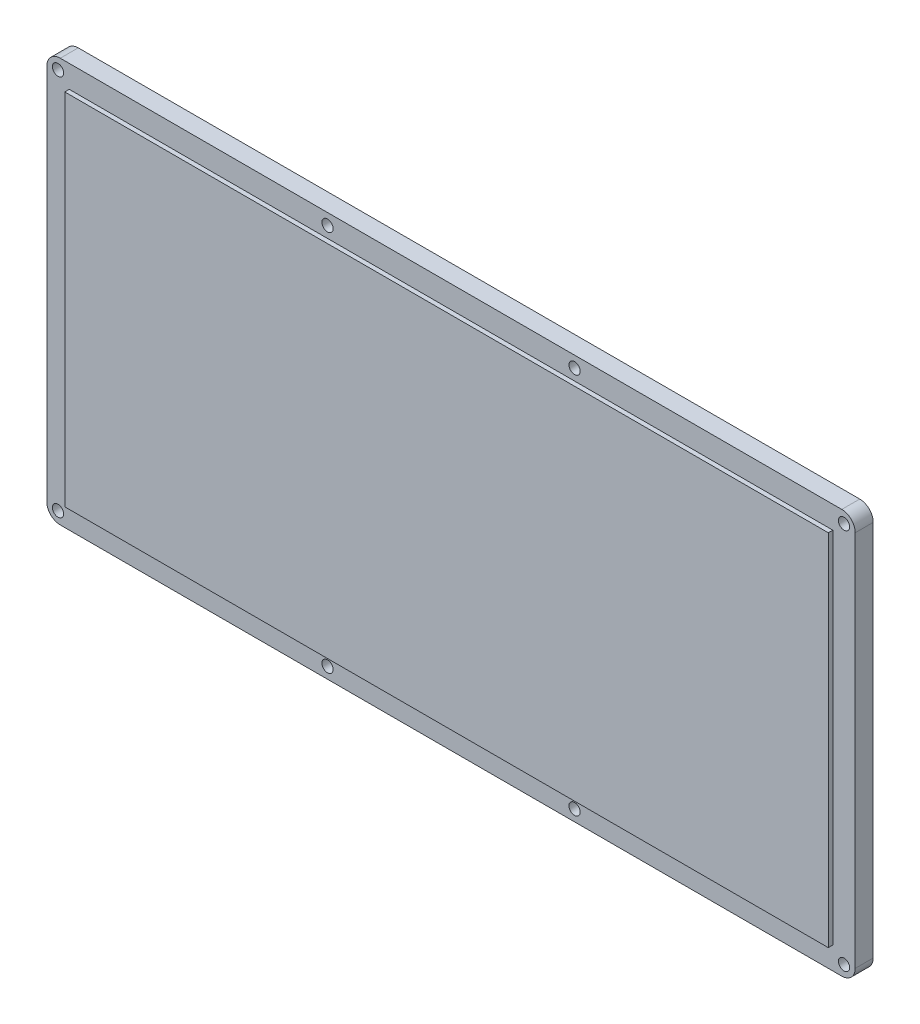
SolidWorks part; units mm, degrees
ref_plane "Front Plane" through (0, 0, 0) normal (0, 0, 1) x (1, 0, 0)
ref_plane "Top Plane" through (0, 0, 0) normal (0, 1, 0) x (1, 0, 0)
ref_plane "Right Plane" through (0, 0, 0) normal (1, 0, 0) x (0, 0, -1)
sketch "Sketch1" plane through (0, 0, 0) normal (0, 0, 1) x (1, 0, 0)
  line L1 (-90, 45) -> (90, 45)
  line L2 (-90, 45) -> (-90, -45)
  line L3 (-90, -45) -> (90, -45)
  line L4 (90, 45) -> (90, -45)
  point P4 (0, 45)
  point P6 (-90, 0)
  dimension "D1" = 180
  dimension "D2" = 90
extrude "Boss-Extrude1" add sketch "Sketch1" along normal blind 4
fillet "Fillet1" radius 3 4 edges at (90, 45, 2) (90, -45, 2) (-90, -45, 2) (-90, 45, 2)
sketch "Sketch2" plane through (0, 0, 4) normal (0, 0, 1) x (1, 0, 0)
  line L8 (85, -40) -> (85, 40)
  line L9 (85, 40) -> (-85, 40)
  line L10 (-85, 40) -> (-85, -40)
  line L11 (-85, -40) -> (85, -40)
  line L12 (85, -40) -> (85, 40)
  line L13 (85, 40) -> (-85, 40)
  line L14 (-85, 40) -> (-85, -40)
  line L15 (-85, -40) -> (85, -40)
  dimension "D1" = 5
extrude "Boss-Extrude2" add sketch "Sketch2" along normal blind 1
sketch "Sketch3" plane through (0, 0, 0) normal (0, 0, -1) x (-1, 0, 0)
  line L1 (-87.5, 42.5) -> (87.5, 42.5) construction
  line L2 (-87.5, 42.5) -> (-87.5, -42.5) construction
  line L3 (-87.5, -42.5) -> (87.5, -42.5) construction
  line L4 (87.5, 42.5) -> (87.5, -42.5) construction
  line L5 (-90, -42) -> (-90, 42) construction
  line L6 (-87, 45) -> (87, 45) construction
  circle A0 centre (-87.5, 42.5) radius 1.25
  circle A1 centre (87.5, 42.5) radius 1.25
  circle A2 centre (87.5, -42.5) radius 1.25
  circle A3 centre (-87.5, -42.5) radius 1.25
  circle A4 centre (-27.5, -42.5) radius 1.25
  circle A5 centre (27.5, 42.5) radius 1.25
  circle A6 centre (27.5, -42.5) radius 1.25
  circle A7 centre (-27.5, 42.5) radius 1.25
  point P4 (0, 42.5)
  point P6 (-87.5, 0)
  dimension "D1" = 2.5
  dimension "D4" = 2.5
  dimension "D5" = 2.5
  dimension "D6" = 60
  dimension "D7" = 2.5
  dimension "D8" = 60
  dimension "D9" = 60
  dimension "D10" = 2.5
  dimension "D2" = 2.5
  dimension "D3" = 2.5
  dimension "D11" = 60
extrude "Cut-Extrude2" cut sketch "Sketch3" against normal blind 10
sketch "Sketch4" plane through (0, 0, 0) normal (0, 0, -1) x (-1, 0, 0)
  line L0 (33.3333, 100) -> (166.6667, 100) construction
  line L1 (47.5892, 25.146) -> (-47.5892, 25.146)
  line L2 (-71.4139, 1.3212) -> (-71.4139, -1.3212)
  line L3 (-47.5892, -25.146) -> (47.5892, -25.146)
  line L4 (71.4139, -1.3212) -> (71.4139, 1.3212)
  line L5 (-27.9881, -11.6905) -> (-26.7934, -10.7431)
  line L6 (-13.3429, 2.4562) -> (-15.6911, 2.4562)
  line L7 (-5.6806, 7.8767) -> (-6.8547, 6.9073)
  line L8 (-15.6911, 4.0426) -> (-13.3429, 4.0426)
  line L9 (-13.3429, -0.717) -> (-15.6911, -0.717)
  line L10 (-3.3529, 9.8599) -> (-4.5065, 8.8684)
  line L11 (-15.6911, 0.8696) -> (-13.4254, 0.8696)
  line L12 (-25.6812, -9.7075) -> (-24.5277, -8.7158)
  line L13 (-15.6911, -2.3036) -> (-13.4254, -2.3036)
  line L14 (-23.3536, -7.7241) -> (-22.1795, -6.7547)
  line L15 (-13.3429, -3.8901) -> (-15.6911, -3.8901)
  line L16 (-1.046, 11.8431) -> (-2.2406, 10.8955)
  line L17 (24.3308, -5.2744) -> (25.4636, -6.2219)
  line L18 (25.4842, 6.7341) -> (24.3101, 5.828)
  line L19 (26.6583, -7.1282) -> (27.7706, -8.0963)
  line L20 (27.8118, 8.588) -> (26.6583, 7.6612)
  line L21 (28.9242, -9.0232) -> (30.0982, -9.9297)
  line L22 (30.1188, 10.4419) -> (28.9242, 9.5561)
  line L23 (55.4131, -5.2744) -> (56.5459, -6.2219)
  line L24 (56.5664, 6.7341) -> (55.3923, 5.828)
  line L25 (57.7405, -7.1282) -> (58.8529, -8.0963)
  line L26 (58.8941, 8.588) -> (57.7405, 7.6612)
  line L27 (60.0064, -9.0232) -> (61.1805, -9.9297)
  line L28 (61.201, 10.4419) -> (60.0064, 9.5561)
  spline S0 degree 3 poles (-35.6815, 4.87) (-36.3065, 6.3326) (-37.151, 7.5957) (-38.2151, 8.6602) knots 15 15 15 15 16 16 16 16
  spline S1 degree 3 poles (-35.6815, -4.3373) (-35.0569, -2.8747) (-34.7443, -1.3401) (-34.7443, 0.2666) (-34.7443, 1.8732) (-35.0569, 3.4076) (-35.6815, 4.87) knots 13 13 13 13 14 14 14 15 15 15 15
  spline S2 degree 3 poles (-38.2151, -8.1271) (-37.151, -7.0632) (-36.3065, -5.7996) (-35.6815, -4.3373) knots 12 12 12 12 13 13 13 13
  spline S3 degree 3 poles (-42.0051, -10.6608) (-40.5426, -10.0362) (-39.2794, -9.1916) (-38.2151, -8.1271) knots 11 11 11 11 12 12 12 12
  spline S4 degree 3 poles (-51.2124, -10.6608) (-49.7499, -11.2858) (-48.2153, -11.5979) (-46.6087, -11.5979) (-45.0021, -11.5979) (-43.4676, -11.2858) (-42.0051, -10.6608) knots 9 9 9 9 10 10 10 11 11 11 11
  spline S5 degree 3 poles (-55.0024, -8.1271) (-53.9384, -9.1916) (-52.6748, -10.0362) (-51.2124, -10.6608) knots 8 8 8 8 9 9 9 9
  spline S6 degree 3 poles (-57.536, -4.3373) (-56.9113, -5.7996) (-56.0668, -7.0632) (-55.0024, -8.1271) knots 7 7 7 7 8 8 8 8
  spline S7 degree 3 poles (-57.536, 4.87) (-58.161, 3.4076) (-58.4732, 1.8732) (-58.4732, 0.2666) (-58.4732, -1.3401) (-58.161, -2.8747) (-57.536, -4.3373) knots 5 5 5 5 6 6 6 7 7 7 7
  spline S8 degree 3 poles (-55.0024, 8.6602) (-56.0668, 7.5957) (-56.9113, 6.3326) (-57.536, 4.87) knots 4 4 4 4 5 5 5 5
  spline S9 degree 3 poles (-51.2124, 11.1937) (-52.6748, 10.5686) (-53.9384, 9.7242) (-55.0024, 8.6602) knots 3 3 3 3 4 4 4 4
  spline S10 degree 3 poles (-42.0051, 11.1937) (-43.4676, 11.8185) (-45.0021, 12.131) (-46.6087, 12.131) (-48.2153, 12.131) (-49.7499, 11.8185) (-51.2124, 11.1937) knots 1 1 1 1 2 2 2 3 3 3 3
  spline S11 degree 3 poles (-38.2151, 8.6602) (-39.2794, 9.7242) (-40.5426, 10.5686) (-42.0051, 11.1937) knots 0 0 0 0 1 1 1 1
  spline S12 degree 3 poles (-37.6177, 5.4777) (-36.6908, 3.8845) (-36.2274, 2.1477) (-36.2274, 0.2666) (-36.2274, -1.615) (-36.6908, -3.3521) (-37.6177, -4.9448) knots 10 10 10 10 11 11 11 12 12 12 12
  spline S13 degree 3 poles (-41.3974, 9.2574) (-39.8046, 8.3307) (-38.5446, 7.0706) (-37.6177, 5.4777) knots 9 9 9 9 10 10 10 10
  spline S14 degree 3 poles (-51.82, 9.2574) (-50.2272, 10.1844) (-48.4903, 10.6479) (-46.6087, 10.6479) (-44.7275, 10.6479) (-42.9906, 10.1844) (-41.3974, 9.2574) knots 7 7 7 7 8 8 8 9 9 9 9
  spline S15 degree 3 poles (-55.5998, 5.4777) (-54.6728, 7.0706) (-53.4132, 8.3307) (-51.82, 9.2574) knots 6 6 6 6 7 7 7 7
  spline S16 degree 3 poles (-55.5998, -4.9448) (-56.5267, -3.3521) (-56.9902, -1.615) (-56.9902, 0.2666) (-56.9902, 2.1477) (-56.5267, 3.8845) (-55.5998, 5.4777) knots 4 4 4 4 5 5 5 6 6 6 6
  spline S17 degree 3 poles (-51.82, -8.7246) (-53.4132, -7.7976) (-54.6728, -6.5379) (-55.5998, -4.9448) knots 3 3 3 3 4 4 4 4
  spline S18 degree 3 poles (-41.3974, -8.7246) (-42.9906, -9.6515) (-44.7275, -10.115) (-46.6087, -10.115) (-48.4903, -10.115) (-50.2272, -9.6515) (-51.82, -8.7246) knots 1 1 1 1 2 2 2 3 3 3 3
  spline S19 degree 3 poles (-37.6177, -4.9448) (-38.5446, -6.5379) (-39.8046, -7.7976) (-41.3974, -8.7246) knots 0 0 0 0 1 1 1 1
  spline S20 degree 3 poles (-40.3161, 6.5488) (-42.0534, 8.2926) (-44.1508, 9.1648) (-46.6087, 9.1648) knots 7 7 7 7 8 8 8 8
  spline S21 degree 3 poles (-40.3161, -6.0159) (-38.579, -4.2722) (-37.7104, -2.178) (-37.7104, 0.2666) (-37.7104, 2.7104) (-38.579, 4.8048) (-40.3161, 6.5488) knots 5 5 5 5 6 6 6 7 7 7 7
  spline S22 degree 3 poles (-52.9015, -6.0159) (-51.1644, -7.76) (-49.0669, -8.6319) (-46.6087, -8.6319) (-44.1508, -8.6319) (-42.0534, -7.76) (-40.3161, -6.0159) knots 3 3 3 3 4 4 4 5 5 5 5
  spline S23 degree 3 poles (-52.9015, 6.5488) (-54.6388, 4.8048) (-55.5071, 2.7104) (-55.5071, 0.2666) (-55.5071, -2.178) (-54.6388, -4.2722) (-52.9015, -6.0159) knots 1 1 1 1 2 2 2 3 3 3 3
  spline S24 degree 3 poles (-46.6087, 9.1648) (-49.0669, 9.1648) (-51.1644, 8.2926) (-52.9015, 6.5488) knots 0 0 0 0 1 1 1 1
  spline S25 degree 3 poles (-32.9523, 6.0236) (-33.735, 7.8567) (-34.7891, 9.4359) (-36.1141, 10.7612) knots 15 15 15 15 16 16 16 16
  spline S26 degree 3 poles (-32.9523, -5.4906) (-32.1696, -3.6575) (-31.7782, -1.7385) (-31.7782, 0.2666) (-31.7782, 2.2713) (-32.1696, 4.1904) (-32.9523, 6.0236) knots 13 13 13 13 14 14 14 15 15 15 15
  spline S27 degree 3 poles (-36.1141, -10.2282) (-34.7891, -8.9031) (-33.735, -7.324) (-32.9523, -5.4906) knots 12 12 12 12 13 13 13 13
  spline S28 degree 3 poles (-40.8516, -13.39) (-39.0184, -12.6074) (-37.4394, -11.5535) (-36.1141, -10.2282) knots 11 11 11 11 12 12 12 12
  spline S29 degree 3 poles (-52.3659, -13.39) (-50.5327, -14.1726) (-48.6138, -14.5641) (-46.6087, -14.5641) (-44.604, -14.5641) (-42.6848, -14.1726) (-40.8516, -13.39) knots 9 9 9 9 10 10 10 11 11 11 11
  spline S30 degree 3 poles (-57.1034, -10.2282) (-55.7784, -11.5535) (-54.1991, -12.6074) (-52.3659, -13.39) knots 8 8 8 8 9 9 9 9
  spline S31 degree 3 poles (-60.2652, -5.4906) (-59.4825, -7.324) (-58.4288, -8.9031) (-57.1034, -10.2282) knots 7 7 7 7 8 8 8 8
  spline S32 degree 3 poles (-60.2652, 6.0236) (-61.0479, 4.1904) (-61.4393, 2.2713) (-61.4393, 0.2666) (-61.4393, -1.7385) (-61.0479, -3.6575) (-60.2652, -5.4906) knots 5 5 5 5 6 6 6 7 7 7 7
  spline S33 degree 3 poles (-57.1034, 10.7612) (-58.4288, 9.4359) (-59.4825, 7.8567) (-60.2652, 6.0236) knots 4 4 4 4 5 5 5 5
  spline S34 degree 3 poles (-52.3659, 13.9229) (-54.1991, 13.1401) (-55.7784, 12.0861) (-57.1034, 10.7612) knots 3 3 3 3 4 4 4 4
  spline S35 degree 3 poles (-40.8516, 13.9229) (-42.6848, 14.7057) (-44.604, 15.097) (-46.6087, 15.097) (-48.6138, 15.097) (-50.5327, 14.7057) (-52.3659, 13.9229) knots 1 1 1 1 2 2 2 3 3 3 3
  spline S36 degree 3 poles (-36.1141, 10.7612) (-37.4394, 12.0861) (-39.0184, 13.1401) (-40.8516, 13.9229) knots 0 0 0 0 1 1 1 1
  spline S37 degree 3 poles (-34.322, 5.457) (-33.615, 3.8093) (-33.2613, 2.0792) (-33.2613, 0.2666) (-33.2613, -1.5461) (-33.615, -3.2764) (-34.322, -4.9243) knots 14 14 14 14 15 15 15 16 16 16 16
  spline S38 degree 3 poles (-37.1646, 9.7106) (-35.9769, 8.5228) (-35.0295, 7.1051) (-34.322, 5.457) knots 13 13 13 13 14 14 14 14
  spline S39 degree 3 poles (-41.418, 12.5531) (-39.7702, 11.8456) (-38.3525, 10.8983) (-37.1646, 9.7106) knots 12 12 12 12 13 13 13 13
  spline S40 degree 3 poles (-51.7994, 12.5531) (-50.1516, 13.2602) (-48.4214, 13.6139) (-46.6087, 13.6139) (-44.7961, 13.6139) (-43.0659, 13.2602) (-41.418, 12.5531) knots 10 10 10 10 11 11 11 12 12 12 12
  spline S41 degree 3 poles (-56.053, 9.7106) (-54.8653, 10.8983) (-53.4473, 11.8456) (-51.7994, 12.5531) knots 9 9 9 9 10 10 10 10
  spline S42 degree 3 poles (-58.8954, 5.457) (-58.1884, 7.1051) (-57.2409, 8.5228) (-56.053, 9.7106) knots 8 8 8 8 9 9 9 9
  spline S43 degree 3 poles (-58.8954, -4.9243) (-59.6029, -3.2764) (-59.9563, -1.5461) (-59.9563, 0.2666) (-59.9563, 2.0792) (-59.6029, 3.8093) (-58.8954, 5.457) knots 6 6 6 6 7 7 7 8 8 8 8
  spline S44 degree 3 poles (-56.053, -9.1777) (-57.2409, -7.99) (-58.1884, -6.572) (-58.8954, -4.9243) knots 5 5 5 5 6 6 6 6
  spline S45 degree 3 poles (-51.7994, -12.0203) (-53.4473, -11.3132) (-54.8653, -10.3657) (-56.053, -9.1777) knots 4 4 4 4 5 5 5 5
  spline S46 degree 3 poles (-41.418, -12.0203) (-43.0659, -12.7276) (-44.7961, -13.081) (-46.6087, -13.081) (-48.4214, -13.081) (-50.1516, -12.7276) (-51.7994, -12.0203) knots 2 2 2 2 3 3 3 4 4 4 4
  spline S47 degree 3 poles (-37.1646, -9.1777) (-38.3525, -10.3657) (-39.7702, -11.3132) (-41.418, -12.0203) knots 1 1 1 1 2 2 2 2
  spline S48 degree 3 poles (-34.322, -4.9243) (-35.0295, -6.572) (-35.9769, -7.99) (-37.1646, -9.1777) knots 0 0 0 0 1 1 1 1
  spline S49 degree 3 poles (-47.5892, 25.146) (-60.7472, 25.146) (-71.4139, 14.4793) (-71.4139, 1.3212) knots 1 1 1 1 2 2 2 2
  spline S50 degree 3 poles (-71.4139, -1.3212) (-71.4139, -14.4793) (-60.7472, -25.146) (-47.5892, -25.146) knots 3 3 3 3 4 4 4 4
  spline S51 degree 3 poles (47.5892, -25.146) (60.7472, -25.146) (71.4139, -14.4793) (71.4139, -1.3212) knots 5 5 5 5 6 6 6 6
  spline S52 degree 3 poles (71.4139, 1.3212) (71.4139, 14.4793) (60.7472, 25.146) (47.5892, 25.146) knots 7 7 7 7 8 8 8 8
  spline S53 degree 3 poles (-31.5928, 6.6003) (-30.7277, 4.5885) (-30.2952, 2.4773) (-30.2952, 0.2666) (-30.2952, -1.9445) (-30.7277, -4.0559) (-31.5928, -6.0674) knots 14 14 14 14 15 15 15 16 16 16 16
  spline S54 degree 3 poles (-35.0739, 11.8015) (-33.6185, 10.3457) (-32.4579, 8.6118) (-31.5928, 6.6003) knots 13 13 13 13 14 14 14 14
  spline S55 degree 3 poles (-40.2748, 15.2823) (-38.2633, 14.4172) (-36.5296, 13.2567) (-35.0739, 11.8015) knots 12 12 12 12 13 13 13 13
  spline S56 degree 3 poles (-52.9426, 15.2823) (-50.9311, 16.1474) (-48.8198, 16.5799) (-46.6087, 16.5799) (-44.398, 16.5799) (-42.2867, 16.1474) (-40.2748, 15.2823) knots 10 10 10 10 11 11 11 12 12 12 12
  spline S57 degree 3 poles (-58.1436, 11.8015) (-56.6882, 13.2567) (-54.9545, 14.4172) (-52.9426, 15.2823) knots 9 9 9 9 10 10 10 10
  spline S58 degree 3 poles (-61.6247, 6.6003) (-60.7596, 8.6118) (-59.5993, 10.3457) (-58.1436, 11.8015) knots 8 8 8 8 9 9 9 9
  spline S59 degree 3 poles (-61.6247, -6.0674) (-62.4897, -4.0559) (-62.9224, -1.9445) (-62.9224, 0.2666) (-62.9224, 2.4773) (-62.4897, 4.5885) (-61.6247, 6.6003) knots 6 6 6 6 7 7 7 8 8 8 8
  spline S60 degree 3 poles (-58.1436, -11.2684) (-59.5993, -9.8131) (-60.7596, -8.0793) (-61.6247, -6.0674) knots 5 5 5 5 6 6 6 6
  spline S61 degree 3 poles (-52.9426, -14.7496) (-54.9545, -13.8845) (-56.6882, -12.7241) (-58.1436, -11.2684) knots 4 4 4 4 5 5 5 5
  spline S62 degree 3 poles (-40.2748, -14.7496) (-42.2867, -15.6146) (-44.398, -16.0472) (-46.6087, -16.0472) (-48.8198, -16.0472) (-50.9311, -15.6146) (-52.9426, -14.7496) knots 2 2 2 2 3 3 3 4 4 4 4
  spline S63 degree 3 poles (-35.0739, -11.2684) (-36.5296, -12.7241) (-38.2633, -13.8845) (-40.2748, -14.7496) knots 1 1 1 1 2 2 2 2
  spline S64 degree 3 poles (-31.5928, -6.0674) (-32.4579, -8.0793) (-33.6185, -9.8131) (-35.0739, -11.2684) knots 0 0 0 0 1 1 1 1
  spline S65 degree 3 poles (-2.2818, -10.2141) (-2.8724, -11.4629) (-3.7206, -12.5609) (-4.8258, -13.5083) knots 0 0 0 0 1 1 1 1
  spline S66 degree 3 poles (-4.8258, -13.5083) (-5.9313, -14.456) (-7.3422, -15.205) (-9.0586, -15.756) knots 1 1 1 1 2 2 2 2
  spline S67 degree 3 poles (-9.0586, -15.756) (-10.7754, -16.3069) (-12.6839, -16.5824) (-14.7848, -16.5824) knots 2 2 2 2 3 3 3 3
  spline S68 degree 3 poles (-14.7848, -16.5824) (-17.4352, -16.5824) (-19.9137, -16.1526) (-22.2207, -15.2933) knots 3 3 3 3 4 4 4 4
  spline S69 degree 3 poles (-22.2207, -15.2933) (-24.5277, -14.4339) (-26.4504, -13.233) (-27.9881, -11.6905) knots 4 4 4 4 5 5 5 5
  spline S70 degree 3 poles (-26.7934, -10.7431) (-25.3928, -12.0948) (-23.6419, -13.1414) (-21.541, -13.8831) knots 6 6 6 6 7 7 7 7
  spline S71 degree 3 poles (-21.541, -13.8831) (-19.4399, -14.625) (-17.1881, -14.9958) (-14.7848, -14.9958) knots 7 7 7 7 8 8 8 8
  spline S72 degree 3 poles (-14.7848, -14.9958) (-11.0773, -14.9958) (-8.166, -14.1584) (-6.0513, -12.4838) knots 8 8 8 8 9 9 9 9
  spline S73 degree 3 poles (-6.0513, -12.4838) (-3.9368, -10.809) (-2.8791, -8.7158) (-2.8791, -6.2038) knots 9 9 9 9 10 10 10 10
  spline S74 degree 3 poles (-2.8791, -6.2038) (-2.8791, -3.5451) (-3.7855, -1.4369) (-5.5981, 0.1202) knots 10 10 10 10 11 11 11 11
  spline S75 degree 3 poles (-5.5981, 0.1202) (-7.4107, 1.6774) (-9.9926, 2.4562) (-13.3429, 2.4562) knots 11 11 11 11 12 12 12 12
  spline S76 degree 3 poles (-15.6911, 2.4562) (-19.701, 2.4562) (-21.7057, 3.7561) (-21.7057, 6.3563) knots 13 13 13 13 14 14 14 14
  spline S77 degree 3 poles (-21.7057, 6.3563) (-21.7057, 7.5314) (-21.0846, 8.4972) (-19.8416, 9.254) knots 14 14 14 14 15 15 15 15
  spline S78 degree 3 poles (-19.8416, 9.254) (-18.599, 10.0105) (-16.7349, 10.3887) (-14.2493, 10.3887) knots 15 15 15 15 16 16 16 16
  spline S79 degree 3 poles (-14.2493, 10.3887) (-12.5055, 10.3887) (-10.885, 10.1718) (-9.3881, 9.7387) knots 16 16 16 16 17 17 17 17
  spline S80 degree 3 poles (-9.3881, 9.7387) (-7.8916, 9.3052) (-6.6558, 8.6845) (-5.6806, 7.8767) knots 17 17 17 17 18 18 18 18
  spline S81 degree 3 poles (-6.8547, 6.9073) (-8.5713, 8.1704) (-11.036, 8.8021) (-14.2493, 8.8021) knots 19 19 19 19 20 20 20 20
  spline S82 degree 3 poles (-14.2493, 8.8021) (-16.3091, 8.8021) (-17.8198, 8.5743) (-18.7809, 8.119) knots 20 20 20 20 21 21 21 21
  spline S83 degree 3 poles (-18.7809, 8.119) (-19.7422, 7.6637) (-20.2227, 7.0759) (-20.2227, 6.3563) knots 21 21 21 21 22 22 22 22
  spline S84 degree 3 poles (-20.2227, 6.3563) (-20.2227, 5.5189) (-19.8864, 4.9239) (-19.2134, 4.5713) knots 22 22 22 22 23 23 23 23
  spline S85 degree 3 poles (-19.2134, 4.5713) (-18.5408, 4.2188) (-17.3667, 4.0426) (-15.6911, 4.0426) knots 23 23 23 23 24 24 24 24
  spline S86 degree 3 poles (-13.3429, 4.0426) (-9.5256, 4.0426) (-6.5801, 3.1132) (-4.5065, 1.2552) knots 25 25 25 25 26 26 26 26
  spline S87 degree 3 poles (-4.5065, 1.2552) (-2.4332, -0.6035) (-1.3962, -3.0896) (-1.3962, -6.2038) knots 26 26 26 26 27 27 27 27
  spline S88 degree 3 poles (-1.3962, -6.2038) (-1.3962, -7.6288) (-1.6917, -8.9657) (-2.2818, -10.2141) knots 27 27 27 27 28 28 28 28
  spline S89 degree 3 poles (-7.73, -2.1383) (-8.9866, -1.1909) (-10.8577, -0.717) (-13.3429, -0.717) knots 0 0 0 0 1 1 1 1
  spline S90 degree 3 poles (-15.6911, -0.717) (-18.5749, -0.717) (-20.7926, -0.089) (-22.3443, 1.167) knots 2 2 2 2 3 3 3 3
  spline S91 degree 3 poles (-22.3443, 1.167) (-23.8962, 2.423) (-24.6719, 4.1527) (-24.6719, 6.3563) knots 3 3 3 3 4 4 4 4
  spline S92 degree 3 poles (-24.6719, 6.3563) (-24.6719, 8.4127) (-23.7588, 10.1277) (-21.9324, 11.5014) knots 4 4 4 4 5 5 5 5
  spline S93 degree 3 poles (-21.9324, 11.5014) (-20.1062, 12.875) (-17.5449, 13.5618) (-14.2493, 13.5618) knots 5 5 5 5 6 6 6 6
  spline S94 degree 3 poles (-14.2493, 13.5618) (-12.0523, 13.5618) (-10.0028, 13.2385) (-8.1008, 12.5921) knots 6 6 6 6 7 7 7 7
  spline S95 degree 3 poles (-8.1008, 12.5921) (-6.1991, 11.9457) (-4.6164, 11.0349) (-3.3529, 9.8599) knots 7 7 7 7 8 8 8 8
  spline S96 degree 3 poles (-4.5065, 8.8684) (-5.6325, 9.8522) (-7.0471, 10.6163) (-8.7496, 11.16) knots 9 9 9 9 10 10 10 10
  spline S97 degree 3 poles (-8.7496, 11.16) (-10.4524, 11.7031) (-12.2858, 11.9753) (-14.2493, 11.9753) knots 10 10 10 10 11 11 11 11
  spline S98 degree 3 poles (-14.2493, 11.9753) (-17.1468, 11.9753) (-19.3611, 11.4463) (-20.8922, 10.3887) knots 11 11 11 11 12 12 12 12
  spline S99 degree 3 poles (-20.8922, 10.3887) (-22.4235, 9.3311) (-23.1889, 7.9868) (-23.1889, 6.3563) knots 12 12 12 12 13 13 13 13
  spline S100 degree 3 poles (-23.1889, 6.3563) (-23.1889, 4.5935) (-22.5606, 3.2383) (-21.3041, 2.2909) knots 13 13 13 13 14 14 14 14
  spline S101 degree 3 poles (-21.3041, 2.2909) (-20.0476, 1.3433) (-18.1768, 0.8696) (-15.6911, 0.8696) knots 14 14 14 14 15 15 15 15
  spline S102 degree 3 poles (-13.4254, 0.8696) (-10.5005, 0.8696) (-8.2588, 0.2416) (-6.7001, -1.0144) knots 16 16 16 16 17 17 17 17
  spline S103 degree 3 poles (-6.7001, -1.0144) (-5.1417, -2.2704) (-4.3622, -4.0003) (-4.3622, -6.2038) knots 17 17 17 17 18 18 18 18
  spline S104 degree 3 poles (-4.3622, -6.2038) (-4.3622, -8.2605) (-5.2757, -9.9755) (-7.1017, -11.349) knots 18 18 18 18 19 19 19 19
  spline S105 degree 3 poles (-7.1017, -11.349) (-8.9283, -12.7228) (-11.4891, -13.4092) (-14.7848, -13.4092) knots 19 19 19 19 20 20 20 20
  spline S106 degree 3 poles (-14.7848, -13.4092) (-16.9821, -13.4092) (-19.0316, -13.0863) (-20.9333, -12.4397) knots 20 20 20 20 21 21 21 21
  spline S107 degree 3 poles (-20.9333, -12.4397) (-22.8354, -11.7934) (-24.4179, -10.8827) (-25.6812, -9.7075) knots 21 21 21 21 22 22 22 22
  spline S108 degree 3 poles (-24.5277, -8.7158) (-23.4019, -9.7) (-21.9873, -10.4641) (-20.2845, -11.0074) knots 23 23 23 23 24 24 24 24
  spline S109 degree 3 poles (-20.2845, -11.0074) (-18.5819, -11.5511) (-16.7487, -11.8227) (-14.7848, -11.8227) knots 24 24 24 24 25 25 25 25
  spline S110 degree 3 poles (-14.7848, -11.8227) (-11.8875, -11.8227) (-9.6733, -11.2939) (-8.142, -10.2361) knots 25 25 25 25 26 26 26 26
  spline S111 degree 3 poles (-8.142, -10.2361) (-6.6109, -9.1785) (-5.8453, -7.8343) (-5.8453, -6.2038) knots 26 26 26 26 27 27 27 27
  spline S112 degree 3 poles (-5.8453, -6.2038) (-5.8453, -4.4409) (-6.4736, -3.0857) (-7.73, -2.1383) knots 27 27 27 27 28 28 28 28
  spline S113 degree 3 poles (-2.2406, 10.8955) (-3.6414, 12.247) (-5.3921, 13.2934) (-7.4932, 14.0355) knots 0 0 0 0 1 1 1 1
  spline S114 degree 3 poles (-7.4932, 14.0355) (-9.5941, 14.7773) (-11.8465, 15.1484) (-14.2493, 15.1484) knots 1 1 1 1 2 2 2 2
  spline S115 degree 3 poles (-14.2493, 15.1484) (-17.9569, 15.1484) (-20.8683, 14.311) (-22.9828, 12.6364) knots 2 2 2 2 3 3 3 3
  spline S116 degree 3 poles (-22.9828, 12.6364) (-25.0976, 10.9616) (-26.1549, 8.8684) (-26.1549, 6.3563) knots 3 3 3 3 4 4 4 4
  spline S117 degree 3 poles (-26.1549, 6.3563) (-26.1549, 3.6973) (-25.2486, 1.5892) (-23.436, 0.0322) knots 4 4 4 4 5 5 5 5
  spline S118 degree 3 poles (-23.436, 0.0322) (-21.6234, -1.5252) (-19.0419, -2.3036) (-15.6911, -2.3036) knots 5 5 5 5 6 6 6 6
  spline S119 degree 3 poles (-13.4254, -2.3036) (-9.3608, -2.3036) (-7.3284, -3.6035) (-7.3284, -6.2038) knots 7 7 7 7 8 8 8 8
  spline S120 degree 3 poles (-7.3284, -6.2038) (-7.3284, -7.3792) (-7.9497, -8.345) (-9.1924, -9.1014) knots 8 8 8 8 9 9 9 9
  spline S121 degree 3 poles (-9.1924, -9.1014) (-10.4354, -9.8582) (-12.2995, -10.2361) (-14.7848, -10.2361) knots 9 9 9 9 10 10 10 10
  spline S122 degree 3 poles (-14.7848, -10.2361) (-16.5289, -10.2361) (-18.1494, -10.0196) (-19.646, -9.5861) knots 10 10 10 10 11 11 11 11
  spline S123 degree 3 poles (-19.646, -9.5861) (-21.1429, -9.153) (-22.3787, -8.5322) (-23.3536, -7.7241) knots 11 11 11 11 12 12 12 12
  spline S124 degree 3 poles (-22.1795, -6.7547) (-20.4631, -8.0182) (-17.9981, -8.6497) (-14.7848, -8.6497) knots 13 13 13 13 14 14 14 14
  spline S125 degree 3 poles (-14.7848, -8.6497) (-12.7249, -8.6497) (-11.2147, -8.4221) (-10.2532, -7.9666) knots 14 14 14 14 15 15 15 15
  spline S126 degree 3 poles (-10.2532, -7.9666) (-9.2923, -7.5115) (-8.8114, -6.9237) (-8.8114, -6.2038) knots 15 15 15 15 16 16 16 16
  spline S127 degree 3 poles (-8.8114, -6.2038) (-8.8114, -5.3665) (-9.148, -4.7715) (-9.8207, -4.4189) knots 16 16 16 16 17 17 17 17
  spline S128 degree 3 poles (-9.8207, -4.4189) (-10.4937, -4.0662) (-11.6678, -3.8901) (-13.3429, -3.8901) knots 17 17 17 17 18 18 18 18
  spline S129 degree 3 poles (-15.6911, -3.8901) (-19.5089, -3.8901) (-22.4544, -2.9612) (-24.5277, -1.1027) knots 19 19 19 19 20 20 20 20
  spline S130 degree 3 poles (-24.5277, -1.1027) (-26.6013, 0.7557) (-27.638, 3.2416) (-27.638, 6.3563) knots 20 20 20 20 21 21 21 21
  spline S131 degree 3 poles (-27.638, 6.3563) (-27.638, 7.781) (-27.3429, 9.1178) (-26.7523, 10.3667) knots 21 21 21 21 22 22 22 22
  spline S132 degree 3 poles (-26.7523, 10.3667) (-26.162, 11.6151) (-25.314, 12.7134) (-24.2084, 13.6608) knots 22 22 22 22 23 23 23 23
  spline S133 degree 3 poles (-24.2084, 13.6608) (-23.1031, 14.6084) (-21.6923, 15.3576) (-19.9755, 15.9086) knots 23 23 23 23 24 24 24 24
  spline S134 degree 3 poles (-19.9755, 15.9086) (-18.2591, 16.4595) (-16.3503, 16.7348) (-14.2493, 16.7348) knots 24 24 24 24 25 25 25 25
  spline S135 degree 3 poles (-14.2493, 16.7348) (-11.5992, 16.7348) (-9.1204, 16.305) (-6.8134, 15.4458) knots 25 25 25 25 26 26 26 26
  spline S136 degree 3 poles (-6.8134, 15.4458) (-4.5065, 14.5863) (-2.584, 13.3854) (-1.046, 11.8431) knots 26 26 26 26 27 27 27 27
  spline S137 degree 3 poles (11.076, -6.0159) (12.8129, -7.76) (14.9104, -8.6319) (17.3685, -8.6319) knots 0 0 0 0 1 1 1 1
  spline S138 degree 3 poles (17.3685, -8.6319) (18.7417, -8.6319) (20.0393, -8.3331) (21.2616, -7.736) knots 1 1 1 1 2 2 2 2
  spline S139 degree 3 poles (21.2616, -7.736) (22.4837, -7.1385) (23.5068, -6.3181) (24.3308, -5.2744) knots 2 2 2 2 3 3 3 3
  spline S140 degree 3 poles (25.4636, -6.2219) (24.5023, -7.4305) (23.3143, -8.3815) (21.9001, -9.0747) knots 4 4 4 4 5 5 5 5
  spline S141 degree 3 poles (21.9001, -9.0747) (20.4856, -9.7682) (18.9752, -10.115) (17.3685, -10.115) knots 5 5 5 5 6 6 6 6
  spline S142 degree 3 poles (17.3685, -10.115) (15.4872, -10.115) (13.75, -9.6515) (12.1573, -8.7246) knots 6 6 6 6 7 7 7 7
  spline S143 degree 3 poles (12.1573, -8.7246) (10.5643, -7.7976) (9.3046, -6.5379) (8.3776, -4.9448) knots 7 7 7 7 8 8 8 8
  spline S144 degree 3 poles (8.3776, -4.9448) (7.4507, -3.3521) (6.9872, -1.615) (6.9872, 0.2666) knots 8 8 8 8 9 9 9 9
  spline S145 degree 3 poles (6.9872, 0.2666) (6.9872, 2.1477) (7.4507, 3.8845) (8.3776, 5.4777) knots 9 9 9 9 10 10 10 10
  spline S146 degree 3 poles (8.3776, 5.4777) (9.3046, 7.0706) (10.5643, 8.3307) (12.1573, 9.2574) knots 10 10 10 10 11 11 11 11
  spline S147 degree 3 poles (12.1573, 9.2574) (13.75, 10.1844) (15.4872, 10.6479) (17.3685, 10.6479) knots 11 11 11 11 12 12 12 12
  spline S148 degree 3 poles (17.3685, 10.6479) (18.9752, 10.6479) (20.4892, 10.301) (21.9104, 9.6076) knots 12 12 12 12 13 13 13 13
  spline S149 degree 3 poles (21.9104, 9.6076) (23.3317, 8.9141) (24.5229, 7.9562) (25.4842, 6.7341) knots 13 13 13 13 14 14 14 14
  spline S150 degree 3 poles (24.3101, 5.828) (23.4862, 6.8712) (22.4666, 7.6885) (21.2513, 8.2792) knots 15 15 15 15 16 16 16 16
  spline S151 degree 3 poles (21.2513, 8.2792) (20.036, 8.8694) (18.7417, 9.1648) (17.3685, 9.1648) knots 16 16 16 16 17 17 17 17
  spline S152 degree 3 poles (17.3685, 9.1648) (14.9104, 9.1648) (12.8129, 8.2926) (11.076, 6.5488) knots 17 17 17 17 18 18 18 18
  spline S153 degree 3 poles (11.076, 6.5488) (9.3387, 4.8048) (8.4703, 2.7104) (8.4703, 0.2666) knots 18 18 18 18 19 19 19 19
  spline S154 degree 3 poles (8.4703, 0.2666) (8.4703, -2.178) (9.3387, -4.2722) (11.076, -6.0159) knots 19 19 19 19 20 20 20 20
  spline S155 degree 3 poles (22.5594, 10.9362) (20.9388, 11.7325) (19.2087, 12.131) (17.3685, 12.131) knots 0 0 0 0 1 1 1 1
  spline S156 degree 3 poles (17.3685, 12.131) (15.7619, 12.131) (14.2275, 11.8185) (12.7649, 11.1937) knots 1 1 1 1 2 2 2 2
  spline S157 degree 3 poles (12.7649, 11.1937) (11.3025, 10.5686) (10.039, 9.7242) (8.9749, 8.6602) knots 2 2 2 2 3 3 3 3
  spline S158 degree 3 poles (8.9749, 8.6602) (7.9106, 7.5957) (7.066, 6.3326) (6.4414, 4.87) knots 3 3 3 3 4 4 4 4
  spline S159 degree 3 poles (6.4414, 4.87) (5.8164, 3.4076) (5.5041, 1.8732) (5.5041, 0.2666) knots 4 4 4 4 5 5 5 5
  spline S160 degree 3 poles (5.5041, 0.2666) (5.5041, -1.3401) (5.8164, -2.8747) (6.4414, -4.3373) knots 5 5 5 5 6 6 6 6
  spline S161 degree 3 poles (6.4414, -4.3373) (7.066, -5.7996) (7.9106, -7.0632) (8.9749, -8.1271) knots 6 6 6 6 7 7 7 7
  spline S162 degree 3 poles (8.9749, -8.1271) (10.039, -9.1916) (11.3025, -10.0362) (12.7649, -10.6608) knots 7 7 7 7 8 8 8 8
  spline S163 degree 3 poles (12.7649, -10.6608) (14.2275, -11.2858) (15.7619, -11.5979) (17.3685, -11.5979) knots 8 8 8 8 9 9 9 9
  spline S164 degree 3 poles (17.3685, -11.5979) (19.2087, -11.5979) (20.9388, -11.1998) (22.5594, -10.4033) knots 9 9 9 9 10 10 10 10
  spline S165 degree 3 poles (22.5594, -10.4033) (24.1794, -9.6071) (25.5459, -8.5155) (26.6583, -7.1282) knots 10 10 10 10 11 11 11 11
  spline S166 degree 3 poles (27.7706, -8.0963) (26.5208, -9.6482) (24.9899, -10.8668) (23.1772, -11.7524) knots 12 12 12 12 13 13 13 13
  spline S167 degree 3 poles (23.1772, -11.7524) (21.3646, -12.6382) (19.4284, -13.081) (17.3685, -13.081) knots 13 13 13 13 14 14 14 14
  spline S168 degree 3 poles (17.3685, -13.081) (15.5559, -13.081) (13.8257, -12.7276) (12.1779, -12.0203) knots 14 14 14 14 15 15 15 15
  spline S169 degree 3 poles (12.1779, -12.0203) (10.53, -11.3132) (9.112, -10.3657) (7.9245, -9.1777) knots 15 15 15 15 16 16 16 16
  spline S170 degree 3 poles (7.9245, -9.1777) (6.7365, -7.99) (5.7889, -6.572) (5.082, -4.9243) knots 16 16 16 16 17 17 17 17
  spline S171 degree 3 poles (5.082, -4.9243) (4.3745, -3.2764) (4.0212, -1.5461) (4.0212, 0.2666) knots 17 17 17 17 18 18 18 18
  spline S172 degree 3 poles (4.0212, 0.2666) (4.0212, 2.0792) (4.3745, 3.8093) (5.082, 5.457) knots 18 18 18 18 19 19 19 19
  spline S173 degree 3 poles (5.082, 5.457) (5.7889, 7.1051) (6.7365, 8.5228) (7.9245, 9.7106) knots 19 19 19 19 20 20 20 20
  spline S174 degree 3 poles (7.9245, 9.7106) (9.112, 10.8983) (10.53, 11.8456) (12.1779, 12.5531) knots 20 20 20 20 21 21 21 21
  spline S175 degree 3 poles (12.1779, 12.5531) (13.8257, 13.2602) (15.5559, 13.6139) (17.3685, 13.6139) knots 21 21 21 21 22 22 22 22
  spline S176 degree 3 poles (17.3685, 13.6139) (19.442, 13.6139) (21.3884, 13.1676) (23.2082, 12.2751) knots 22 22 22 22 23 23 23 23
  spline S177 degree 3 poles (23.2082, 12.2751) (25.0274, 11.3823) (26.562, 10.1534) (27.8118, 8.588) knots 23 23 23 23 24 24 24 24
  spline S178 degree 3 poles (26.6583, 7.6612) (25.5459, 9.0479) (24.1794, 10.1397) (22.5594, 10.9362) knots 25 25 25 25 26 26 26 26
  spline S179 degree 3 poles (23.826, 13.6139) (21.8142, 14.6027) (19.6617, 15.097) (17.3685, 15.097) knots 0 0 0 0 1 1 1 1
  spline S180 degree 3 poles (17.3685, 15.097) (15.3635, 15.097) (13.4447, 14.7057) (11.6115, 13.9229) knots 1 1 1 1 2 2 2 2
  spline S181 degree 3 poles (11.6115, 13.9229) (9.7782, 13.1401) (8.199, 12.0861) (6.8739, 10.7612) knots 2 2 2 2 3 3 3 3
  spline S182 degree 3 poles (6.8739, 10.7612) (5.5486, 9.4359) (4.4949, 7.8567) (3.7122, 6.0236) knots 3 3 3 3 4 4 4 4
  spline S183 degree 3 poles (3.7122, 6.0236) (2.9294, 4.1904) (2.5381, 2.2713) (2.5381, 0.2666) knots 4 4 4 4 5 5 5 5
  spline S184 degree 3 poles (2.5381, 0.2666) (2.5381, -1.7385) (2.9294, -3.6575) (3.7122, -5.4906) knots 5 5 5 5 6 6 6 6
  spline S185 degree 3 poles (3.7122, -5.4906) (4.4949, -7.324) (5.5486, -8.9031) (6.8739, -10.2282) knots 6 6 6 6 7 7 7 7
  spline S186 degree 3 poles (6.8739, -10.2282) (8.199, -11.5535) (9.7782, -12.6074) (11.6115, -13.39) knots 7 7 7 7 8 8 8 8
  spline S187 degree 3 poles (11.6115, -13.39) (13.4447, -14.1726) (15.3635, -14.5641) (17.3685, -14.5641) knots 8 8 8 8 9 9 9 9
  spline S188 degree 3 poles (17.3685, -14.5641) (19.6617, -14.5641) (21.8142, -14.0698) (23.826, -13.081) knots 9 9 9 9 10 10 10 10
  spline S189 degree 3 poles (23.826, -13.081) (25.8375, -12.0924) (27.5369, -10.7399) (28.9242, -9.0232) knots 10 10 10 10 11 11 11 11
  spline S190 degree 3 poles (30.0982, -9.9297) (28.5739, -11.8244) (26.7026, -13.318) (24.4853, -14.4096) knots 12 12 12 12 13 13 13 13
  spline S191 degree 3 poles (24.4853, -14.4096) (22.2674, -15.5012) (19.8951, -16.0472) (17.3685, -16.0472) knots 13 13 13 13 14 14 14 14
  spline S192 degree 3 poles (17.3685, -16.0472) (15.1575, -16.0472) (13.0463, -15.6146) (11.0347, -14.7496) knots 14 14 14 14 15 15 15 15
  spline S193 degree 3 poles (11.0347, -14.7496) (9.0229, -13.8845) (7.2891, -12.7241) (5.8338, -11.2684) knots 15 15 15 15 16 16 16 16
  spline S194 degree 3 poles (5.8338, -11.2684) (4.378, -9.8131) (3.2179, -8.0793) (2.3526, -6.0674) knots 16 16 16 16 17 17 17 17
  spline S195 degree 3 poles (2.3526, -6.0674) (1.4875, -4.0559) (1.055, -1.9445) (1.055, 0.2666) knots 17 17 17 17 18 18 18 18
  spline S196 degree 3 poles (1.055, 0.2666) (1.055, 2.4773) (1.4875, 4.5885) (2.3526, 6.6003) knots 18 18 18 18 19 19 19 19
  spline S197 degree 3 poles (2.3526, 6.6003) (3.2179, 8.6118) (4.378, 10.3457) (5.8338, 11.8015) knots 19 19 19 19 20 20 20 20
  spline S198 degree 3 poles (5.8338, 11.8015) (7.2891, 13.2567) (9.0229, 14.4172) (11.0347, 15.2823) knots 20 20 20 20 21 21 21 21
  spline S199 degree 3 poles (11.0347, 15.2823) (13.0463, 16.1474) (15.1575, 16.5799) (17.3685, 16.5799) knots 21 21 21 21 22 22 22 22
  spline S200 degree 3 poles (17.3685, 16.5799) (19.8951, 16.5799) (22.2709, 16.0343) (24.4956, 14.9425) knots 22 22 22 22 23 23 23 23
  spline S201 degree 3 poles (24.4956, 14.9425) (26.72, 13.8507) (28.5944, 12.3504) (30.1188, 10.4419) knots 23 23 23 23 24 24 24 24
  spline S202 degree 3 poles (28.9242, 9.5561) (27.5369, 11.2725) (25.8375, 12.6251) (23.826, 13.6139) knots 25 25 25 25 26 26 26 26
  spline S203 degree 3 poles (42.1582, -6.0159) (43.8952, -7.76) (45.9927, -8.6319) (48.4508, -8.6319) knots 0 0 0 0 1 1 1 1
  spline S204 degree 3 poles (48.4508, -8.6319) (49.8239, -8.6319) (51.1216, -8.3331) (52.3439, -7.736) knots 1 1 1 1 2 2 2 2
  spline S205 degree 3 poles (52.3439, -7.736) (53.566, -7.1385) (54.589, -6.3181) (55.4131, -5.2744) knots 2 2 2 2 3 3 3 3
  spline S206 degree 3 poles (56.5459, -6.2219) (55.5846, -7.4305) (54.3966, -8.3815) (52.9824, -9.0747) knots 4 4 4 4 5 5 5 5
  spline S207 degree 3 poles (52.9824, -9.0747) (51.5679, -9.7682) (50.0574, -10.115) (48.4508, -10.115) knots 5 5 5 5 6 6 6 6
  spline S208 degree 3 poles (48.4508, -10.115) (46.5694, -10.115) (44.8323, -9.6515) (43.2396, -8.7246) knots 6 6 6 6 7 7 7 7
  spline S209 degree 3 poles (43.2396, -8.7246) (41.6465, -7.7976) (40.3868, -6.5379) (39.4598, -4.9448) knots 7 7 7 7 8 8 8 8
  spline S210 degree 3 poles (39.4598, -4.9448) (38.533, -3.3521) (38.0695, -1.615) (38.0695, 0.2666) knots 8 8 8 8 9 9 9 9
  spline S211 degree 3 poles (38.0695, 0.2666) (38.0695, 2.1477) (38.533, 3.8845) (39.4598, 5.4777) knots 9 9 9 9 10 10 10 10
  spline S212 degree 3 poles (39.4598, 5.4777) (40.3868, 7.0706) (41.6465, 8.3307) (43.2396, 9.2574) knots 10 10 10 10 11 11 11 11
  spline S213 degree 3 poles (43.2396, 9.2574) (44.8323, 10.1844) (46.5694, 10.6479) (48.4508, 10.6479) knots 11 11 11 11 12 12 12 12
  spline S214 degree 3 poles (48.4508, 10.6479) (50.0574, 10.6479) (51.5715, 10.301) (52.9927, 9.6076) knots 12 12 12 12 13 13 13 13
  spline S215 degree 3 poles (52.9927, 9.6076) (54.414, 8.9141) (55.6051, 7.9562) (56.5664, 6.7341) knots 13 13 13 13 14 14 14 14
  spline S216 degree 3 poles (55.3923, 5.828) (54.5685, 6.8712) (53.5489, 7.6885) (52.3336, 8.2792) knots 15 15 15 15 16 16 16 16
  spline S217 degree 3 poles (52.3336, 8.2792) (51.1183, 8.8694) (49.8239, 9.1648) (48.4508, 9.1648) knots 16 16 16 16 17 17 17 17
  spline S218 degree 3 poles (48.4508, 9.1648) (45.9927, 9.1648) (43.8952, 8.2926) (42.1582, 6.5488) knots 17 17 17 17 18 18 18 18
  spline S219 degree 3 poles (42.1582, 6.5488) (40.4209, 4.8048) (39.5526, 2.7104) (39.5526, 0.2666) knots 18 18 18 18 19 19 19 19
  spline S220 degree 3 poles (39.5526, 0.2666) (39.5526, -2.178) (40.4209, -4.2722) (42.1582, -6.0159) knots 19 19 19 19 20 20 20 20
  spline S221 degree 3 poles (53.6416, 10.9362) (52.0211, 11.7325) (50.2909, 12.131) (48.4508, 12.131) knots 0 0 0 0 1 1 1 1
  spline S222 degree 3 poles (48.4508, 12.131) (46.8442, 12.131) (45.3097, 11.8185) (43.8472, 11.1937) knots 1 1 1 1 2 2 2 2
  spline S223 degree 3 poles (43.8472, 11.1937) (42.3848, 10.5686) (41.1213, 9.7242) (40.0571, 8.6602) knots 2 2 2 2 3 3 3 3
  spline S224 degree 3 poles (40.0571, 8.6602) (38.9928, 7.5957) (38.1483, 6.3326) (37.5236, 4.87) knots 3 3 3 3 4 4 4 4
  spline S225 degree 3 poles (37.5236, 4.87) (36.8987, 3.4076) (36.5864, 1.8732) (36.5864, 0.2666) knots 4 4 4 4 5 5 5 5
  spline S226 degree 3 poles (36.5864, 0.2666) (36.5864, -1.3401) (36.8987, -2.8747) (37.5236, -4.3373) knots 5 5 5 5 6 6 6 6
  spline S227 degree 3 poles (37.5236, -4.3373) (38.1483, -5.7996) (38.9928, -7.0632) (40.0571, -8.1271) knots 6 6 6 6 7 7 7 7
  spline S228 degree 3 poles (40.0571, -8.1271) (41.1213, -9.1916) (42.3848, -10.0362) (43.8472, -10.6608) knots 7 7 7 7 8 8 8 8
  spline S229 degree 3 poles (43.8472, -10.6608) (45.3097, -11.2858) (46.8442, -11.5979) (48.4508, -11.5979) knots 8 8 8 8 9 9 9 9
  spline S230 degree 3 poles (48.4508, -11.5979) (50.2909, -11.5979) (52.0211, -11.1998) (53.6416, -10.4033) knots 9 9 9 9 10 10 10 10
  spline S231 degree 3 poles (53.6416, -10.4033) (55.2617, -9.6071) (56.6282, -8.5155) (57.7405, -7.1282) knots 10 10 10 10 11 11 11 11
  spline S232 degree 3 poles (58.8529, -8.0963) (57.6031, -9.6482) (56.0721, -10.8668) (54.2595, -11.7524) knots 12 12 12 12 13 13 13 13
  spline S233 degree 3 poles (54.2595, -11.7524) (52.4469, -12.6382) (50.5107, -13.081) (48.4508, -13.081) knots 13 13 13 13 14 14 14 14
  spline S234 degree 3 poles (48.4508, -13.081) (46.6382, -13.081) (44.908, -12.7276) (43.2601, -12.0203) knots 14 14 14 14 15 15 15 15
  spline S235 degree 3 poles (43.2601, -12.0203) (41.6123, -11.3132) (40.1942, -10.3657) (39.0068, -9.1777) knots 15 15 15 15 16 16 16 16
  spline S236 degree 3 poles (39.0068, -9.1777) (37.8187, -7.99) (36.8712, -6.572) (36.1642, -4.9243) knots 16 16 16 16 17 17 17 17
  spline S237 degree 3 poles (36.1642, -4.9243) (35.4568, -3.2764) (35.1034, -1.5461) (35.1034, 0.2666) knots 17 17 17 17 18 18 18 18
  spline S238 degree 3 poles (35.1034, 0.2666) (35.1034, 2.0792) (35.4568, 3.8093) (36.1642, 5.457) knots 18 18 18 18 19 19 19 19
  spline S239 degree 3 poles (36.1642, 5.457) (36.8712, 7.1051) (37.8187, 8.5228) (39.0068, 9.7106) knots 19 19 19 19 20 20 20 20
  spline S240 degree 3 poles (39.0068, 9.7106) (40.1942, 10.8983) (41.6123, 11.8456) (43.2601, 12.5531) knots 20 20 20 20 21 21 21 21
  spline S241 degree 3 poles (43.2601, 12.5531) (44.908, 13.2602) (46.6382, 13.6139) (48.4508, 13.6139) knots 21 21 21 21 22 22 22 22
  spline S242 degree 3 poles (48.4508, 13.6139) (50.5243, 13.6139) (52.4707, 13.1676) (54.2905, 12.2751) knots 22 22 22 22 23 23 23 23
  spline S243 degree 3 poles (54.2905, 12.2751) (56.1097, 11.3823) (57.6443, 10.1534) (58.8941, 8.588) knots 23 23 23 23 24 24 24 24
  spline S244 degree 3 poles (57.7405, 7.6612) (56.6282, 9.0479) (55.2617, 10.1397) (53.6416, 10.9362) knots 25 25 25 25 26 26 26 26
  spline S245 degree 3 poles (54.9083, 13.6139) (52.8964, 14.6027) (50.744, 15.097) (48.4508, 15.097) knots 0 0 0 0 1 1 1 1
  spline S246 degree 3 poles (48.4508, 15.097) (46.4457, 15.097) (44.527, 14.7057) (42.6938, 13.9229) knots 1 1 1 1 2 2 2 2
  spline S247 degree 3 poles (42.6938, 13.9229) (40.8604, 13.1401) (39.2813, 12.0861) (37.9562, 10.7612) knots 2 2 2 2 3 3 3 3
  spline S248 degree 3 poles (37.9562, 10.7612) (36.6309, 9.4359) (35.5772, 7.8567) (34.7944, 6.0236) knots 3 3 3 3 4 4 4 4
  spline S249 degree 3 poles (34.7944, 6.0236) (34.0116, 4.1904) (33.6203, 2.2713) (33.6203, 0.2666) knots 4 4 4 4 5 5 5 5
  spline S250 degree 3 poles (33.6203, 0.2666) (33.6203, -1.7385) (34.0116, -3.6575) (34.7944, -5.4906) knots 5 5 5 5 6 6 6 6
  spline S251 degree 3 poles (34.7944, -5.4906) (35.5772, -7.324) (36.6309, -8.9031) (37.9562, -10.2282) knots 6 6 6 6 7 7 7 7
  spline S252 degree 3 poles (37.9562, -10.2282) (39.2813, -11.5535) (40.8604, -12.6074) (42.6938, -13.39) knots 7 7 7 7 8 8 8 8
  spline S253 degree 3 poles (42.6938, -13.39) (44.527, -14.1726) (46.4457, -14.5641) (48.4508, -14.5641) knots 8 8 8 8 9 9 9 9
  spline S254 degree 3 poles (48.4508, -14.5641) (50.744, -14.5641) (52.8964, -14.0698) (54.9083, -13.081) knots 9 9 9 9 10 10 10 10
  spline S255 degree 3 poles (54.9083, -13.081) (56.9198, -12.0924) (58.6192, -10.7399) (60.0064, -9.0232) knots 10 10 10 10 11 11 11 11
  spline S256 degree 3 poles (61.1805, -9.9297) (59.6562, -11.8244) (57.7849, -13.318) (55.5676, -14.4096) knots 12 12 12 12 13 13 13 13
  spline S257 degree 3 poles (55.5676, -14.4096) (53.3497, -15.5012) (50.9773, -16.0472) (48.4508, -16.0472) knots 13 13 13 13 14 14 14 14
  spline S258 degree 3 poles (48.4508, -16.0472) (46.2397, -16.0472) (44.1285, -15.6146) (42.117, -14.7496) knots 14 14 14 14 15 15 15 15
  spline S259 degree 3 poles (42.117, -14.7496) (40.1052, -13.8845) (38.3713, -12.7241) (36.9161, -11.2684) knots 15 15 15 15 16 16 16 16
  spline S260 degree 3 poles (36.9161, -11.2684) (35.4603, -9.8131) (34.3001, -8.0793) (33.4349, -6.0674) knots 16 16 16 16 17 17 17 17
  spline S261 degree 3 poles (33.4349, -6.0674) (32.5698, -4.0559) (32.1372, -1.9445) (32.1372, 0.2666) knots 17 17 17 17 18 18 18 18
  spline S262 degree 3 poles (32.1372, 0.2666) (32.1372, 2.4773) (32.5698, 4.5885) (33.4349, 6.6003) knots 18 18 18 18 19 19 19 19
  spline S263 degree 3 poles (33.4349, 6.6003) (34.3001, 8.6118) (35.4603, 10.3457) (36.9161, 11.8015) knots 19 19 19 19 20 20 20 20
  spline S264 degree 3 poles (36.9161, 11.8015) (38.3713, 13.2567) (40.1052, 14.4172) (42.117, 15.2823) knots 20 20 20 20 21 21 21 21
  spline S265 degree 3 poles (42.117, 15.2823) (44.1285, 16.1474) (46.2397, 16.5799) (48.4508, 16.5799) knots 21 21 21 21 22 22 22 22
  spline S266 degree 3 poles (48.4508, 16.5799) (50.9773, 16.5799) (53.3532, 16.0343) (55.5778, 14.9425) knots 22 22 22 22 23 23 23 23
  spline S267 degree 3 poles (55.5778, 14.9425) (57.8023, 13.8507) (59.6767, 12.3504) (61.201, 10.4419) knots 23 23 23 23 24 24 24 24
  spline S268 degree 3 poles (60.0064, 9.5561) (58.6192, 11.2725) (56.9198, 12.6251) (54.9083, 13.6139) knots 25 25 25 25 26 26 26 26
  point P299 (0, 0)
  point P300 (0, 25.146)
  point P301 (71.4139, 0)
extrude "Boss-Extrude4" add sketch "Sketch4" along normal blind 1 contours S202 L22 S201 S200 S199 S198 S197 S196 S195 S194 S193 S192 S191 S190 L21 S189 S188 S187 S186 S185 S184 S183 S182 S181 S180 S179 | S178 L20 S177 S176 S175 S174 S173 S172 S171 S170 S169 S168 S167 S166 L19 S165 S164 S163 S162 S161 S160 S159 S158 S157 S156 S155 | S154 S153 S152 S151 S150 L18 S149 S148 S147 S146 S145 S144 S143 S142 S141 S140 L17 S139 S138 S137 | S244 L26 S243 S242 S241 S240 S239 S238 S237 S236 S235 S234 S233 S232 L25 S231 S230 S229 S228 S227 S226 S225 S224 S223 S222 S221 | S136 L16 S113 S114 S115 S116 S117 S118 L13 S119 S120 S121 S122 S123 L14 S124 S125 S126 S127 S128 L15 S129 S130 S131 S132 S133 S134 S135 | S50 L3 S51 L4 S52 L1 S49 L2 | S22 S21 S20 S24 S23 | S62 S61 S60 S59 S58 S57 S56 S55 S54 S53 S64 S63 | S4 S3 S2 S1 S0 S11 S10 S9 S8 S7 S6 S5 | S29 S28 S27 S26 S25 S36 S35 S34 S33 S32 S31 S30 | S46 S45 S44 S43 S42 S41 S40 S39 S38 S37 S48 S47 | S18 S17 S16 S15 S14 S13 S12 S19 | S68 S69 L5 S70 S71 S72 S73 S74 S75 L6 S76 S77 S78 S79 S80 L7 S81 S82 S83 S84 S85 L8 S86 S87 S88 S65 S66 S67 | S106 S107 L12 S108 S109 S110 S111 S112 S89 L9 S90 S91 S92 S93 S94 S95 L10 S96 S97 S98 S99 S100 S101 L11 S102 S103 S104 S105 | S252 S253 S254 S255 L27 S256 S257 S258 S259 S260 S261 S262 S263 S264 S265 S266 S267 L28 S268 S245 S246 S247 S248 S249 S250 S251 | S203 S204 S205 L23 S206 S207 S208 S209 S210 S211 S212 S213 S214 S215 L24 S216 S217 S218 S219 S220 region at (-24.7188, -5.9614, 0) region at (-26.9797, -7.882, 0) region at (-29.2442, -9.8223, 0) region at (-58.0619, -7.882, 0)
